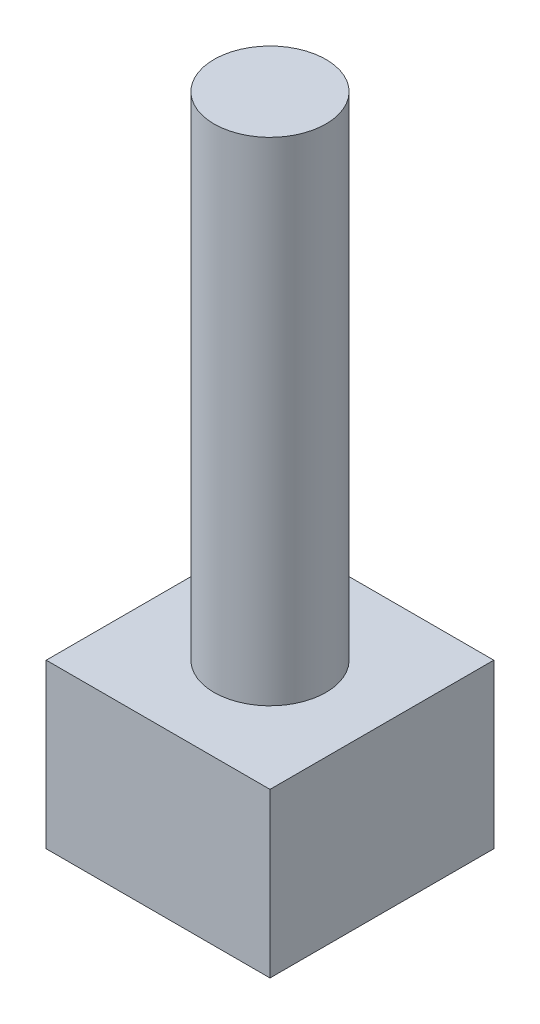
SolidWorks part; units mm, degrees
ref_plane "Front Plane" through (0, 0, 0) normal (0, 0, 1) x (1, 0, 0)
ref_plane "Top Plane" through (0, 0, 0) normal (0, 1, 0) x (1, 0, 0)
ref_plane "Right Plane" through (0, 0, 0) normal (1, 0, 0) x (0, 0, -1)
sketch "Sketch1" plane through (0, 0, 0) normal (0, 1, 0) x (1, 0, 0)
  circle A0 centre (0, 0) radius 6.35
  dimension "D1" = 12.7
extrude "Boss-Extrude1" add sketch "Sketch1" along normal blind 55.88
sketch "Sketch2" plane through (0, 0, 0) normal (0, -1, 0) x (1, 0, 0)
  line L1 (12.7, -12.7) -> (-12.7, -12.7)
  line L2 (12.7, -12.7) -> (12.7, 12.7)
  line L3 (12.7, 12.7) -> (-12.7, 12.7)
  line L4 (-12.7, -12.7) -> (-12.7, 12.7)
  line L5 (12.7, -12.7) -> (-12.7, 12.7) construction
  line L6 (12.7, 12.7) -> (-12.7, -12.7) construction
  point P0 (0, 0)
  dimension "D1" = 25.4
  dimension "D2" = 25.4
extrude "Boss-Extrude2" add sketch "Sketch2" along normal blind 18.542 contours L2 L3 L4 L1
